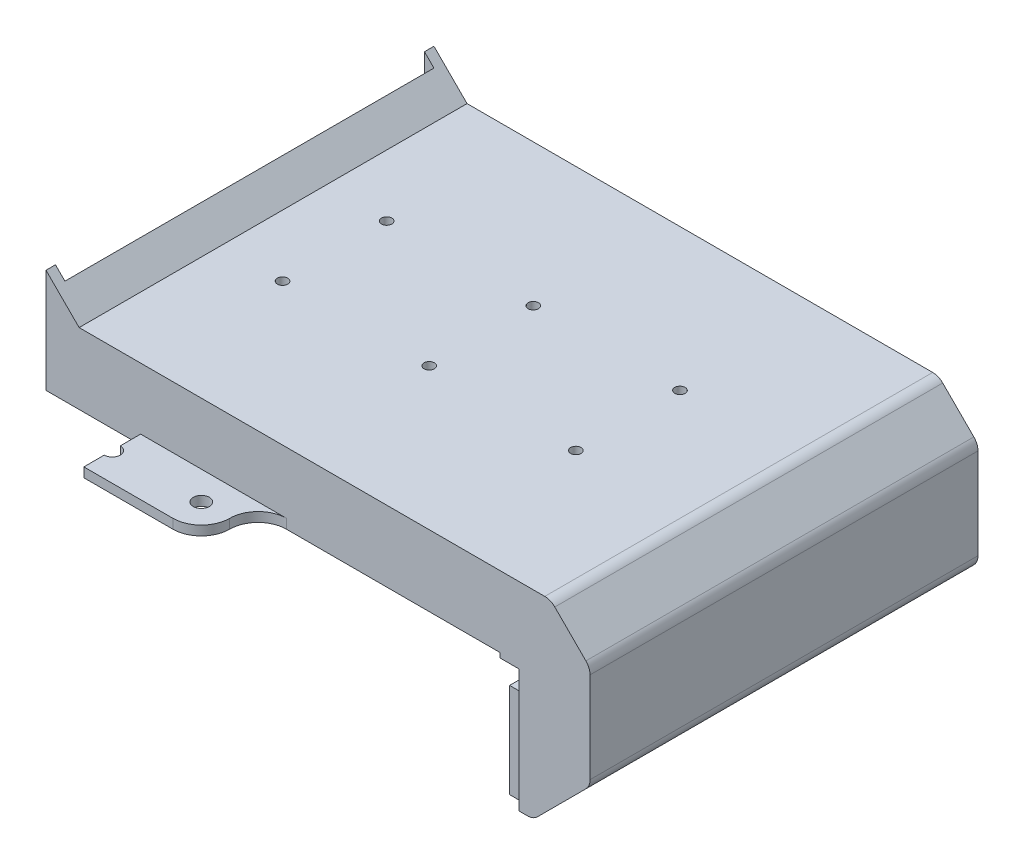
SolidWorks part; units mm, degrees
ref_plane "前视基准面" through (0, 0, 0) normal (0, 0, 1) x (1, 0, 0)
ref_plane "上视基准面" through (0, 0, 0) normal (0, 1, 0) x (1, 0, 0)
ref_plane "右视基准面" through (0, 0, 0) normal (1, 0, 0) x (0, 0, -1)
sketch "草图1" plane through (0, 0, 0) normal (0, 0, 1) x (1, 0, 0)
  line L1 (0, 2) -> (3, 2)
  line L7 (0, 0) -> (3, 0)
  line L15 (3, 2) -> (13, 12)
  line L16 (3, 0) -> (15, 12)
  line L18 (15, 12) -> (15, 33.6667)
  line L21 (13, 12) -> (13, 33.6667)
  line L22 (13, 33.6667) -> (6.6667, 40)
  line L23 (-93, 40) -> (6.6667, 40)
  line L24 (15, 33.6667) -> (6.6667, 42)
  line L25 (-93, 42) -> (6.6667, 42)
  line L26 (0, 0) -> (0, 2)
  line L29 (-98, 47) -> (-93, 42)
  line L30 (-93, 40) -> (-98, 45)
  line L31 (-98, 47) -> (-98, 45)
extrude "凸台-拉伸1" add sketch "草图1" along normal blind 82
fillet "圆角1" radius 3 8 edges at (3, 0, 41) (15, 12, 41) (3, 2, 41) (6.6667, 42, 41) (15, 33.6667, 41) (6.6667, 40, 41) (13, 33.6667, 41) (13, 12, 41)
sketch "草图2" plane through (0, 0, 0) normal (0, 0, -1) x (-1, 0, 0)
  line L2 (104.8261, 27) -> (98.8261, 27) construction
  line L3 (100, 27) -> (100, 49)
  line L4 (100, 49) -> (93, 42)
  line L5 (93, 42) -> (-5.424, 42)
  line L6 (-7.5453, 41.1213) -> (-14.1213, 34.5453)
  line L7 (-15, 32.424) -> (-15, 13.2426)
  line L8 (-14.1213, 11.1213) -> (-3.8787, 0.8787)
  line L9 (0, 0) -> (-1.7574, 0)
  line L10 (0, 26) -> (4, 26)
  line L11 (4, 26) -> (4, 27)
  line L12 (4, 27) -> (100, 27)
  line L13 (0, 26) -> (0, 0)
  arc A0 (-5.424, 42) -> (-7.5453, 41.1213) centre (-5.424, 39) ccw
  arc A1 (-14.1213, 34.5453) -> (-15, 32.424) centre (-12, 32.424) ccw
  arc A2 (-3.8787, 0.8787) -> (-1.7574, 0) centre (-1.7574, 3) ccw
  arc A3 (-15, 13.2426) -> (-14.1213, 11.1213) centre (-12, 13.2426) ccw
extrude "凸台-拉伸2" add sketch "草图2" against normal blind 2
extrude "凸台-拉伸3" add sketch "草图2<2>" along normal blind 2 from surface starting at face at (-10.6868, 23.9394, 82)
sketch "草图2<2>" plane through (0, 0, 0) normal (0, 0, -1) x (-1, 0, 0) same geometry as "草图2"
sketch "草图3" plane through (0, 0, 0) normal (-1, 0, 0) x (0, 0, 1)
  line L0 (1, 1) -> (8, 1)
  line L1 (1, 1) -> (81, 1) construction
  line L2 (8, 1) -> (8, 21)
  line L3 (8, 21) -> (1, 21)
  line L4 (1, 26) -> (1, 3) construction
  line L5 (1, 21) -> (1, 1)
  line L8 (81, 21) -> (81, 1)
  line L9 (74, 21) -> (81, 21)
  line L10 (74, 1) -> (74, 21)
  line L11 (81, 1) -> (74, 1)
extrude "凸台-拉伸4" add sketch "草图3" against normal blind 2
sketch "草图4" plane through (0, 0, 0) normal (-1, 0, 0) x (0, 0, 1)
  line L0 (8, 21) -> (6, 21)
  line L1 (8, 21) -> (2, 21) construction
  line L2 (6, 21) -> (6, 1)
  line L3 (6, 1) -> (8, 1)
  line L4 (8, 1) -> (8, 21)
  line L5 (74, 21) -> (74, 1)
  line L6 (74, 1) -> (76, 1)
  line L7 (76, 1) -> (76, 21)
  line L8 (80, 21) -> (74, 21) construction
  line L9 (76, 21) -> (74, 21)
extrude "凸台-拉伸5" add sketch "草图4" along normal blind 1
sketch "草图5" plane through (-1, 0, 0) normal (-1, 0, 0) x (0, 0, 1)
  line L0 (8, 21) -> (1, 21)
  line L1 (1, 21) -> (1, 1)
  line L2 (1, 1) -> (8, 1)
  line L3 (8, 1) -> (8, 21)
  line L6 (81, 1) -> (74, 1)
  line L7 (74, 1) -> (74, 21)
  line L8 (81, 21) -> (81, 1)
  line L9 (74, 21) -> (81, 21)
extrude "凸台-拉伸6" add sketch "草图5" along normal blind 2
sketch "草图6" plane through (0, 27, 0) normal (0, -1, 0) x (1, 0, 0)
  line L0 (-80, 86.3) -> (-80, 82)
  line L1 (-4, 82) -> (-100, 82) construction
  line L2 (-80, 82) -> (-49.1739, 82)
  line L3 (-80, 89.7) -> (-80, 94)
  line L4 (-61.1739, 94) -> (-98.8261, 94) construction
  line L5 (-80, 94) -> (-61.1739, 94)
  line L8 (-80, -12) -> (-61.1739, -12)
  line L9 (-80, -7.7) -> (-80, -12)
  line L10 (-80, 0) -> (-49.1739, 0)
  line L11 (-80, -4.3) -> (-80, 0)
  circle A0 centre (-80, 88) radius 1.7 construction
  arc A1 (-55.1739, 88) -> (-49.1739, 82) centre (-49.1739, 88) ccw construction
  arc A2 (-80, 86.3) -> (-80, 89.7) centre (-80, 88) ccw
  arc A3 (-55.1739, 88) -> (-61.1739, 94) centre (-61.1739, 88) ccw
  arc A5 (-55.1739, 88) -> (-49.1739, 82) centre (-49.1739, 88) ccw
  circle A6 centre (-61.1739, 88) radius 1.7
  circle A7 centre (-61.1739, -6) radius 1.7
  arc A8 (-55.1739, -6) -> (-49.1739, 0) centre (-49.1739, -6) cw
  arc A9 (-55.1739, -6) -> (-61.1739, -12) centre (-61.1739, -6) cw
  arc A10 (-80, -4.3) -> (-80, -7.7) centre (-80, -6) cw
extrude "凸台-拉伸7" add sketch "草图6" against normal blind 2
sketch "草图7" plane through (0, 42, 0) normal (0, 1, 0) x (1, 0, 0)
  circle A0 centre (-49, -30) radius 1.1
  circle A1 centre (-80, -30) radius 1.1
  circle A2 centre (-80, -52) radius 1.1
  circle A3 centre (-49, -52) radius 1.1
  circle A4 centre (-18, -30) radius 1.1
  circle A5 centre (-18, -52) radius 1.1
  point P13 (-18.5403, -30)
  point P15 (-17.2979, -52)
extrude "切除-拉伸1" cut sketch "草图7" against normal blind 2
